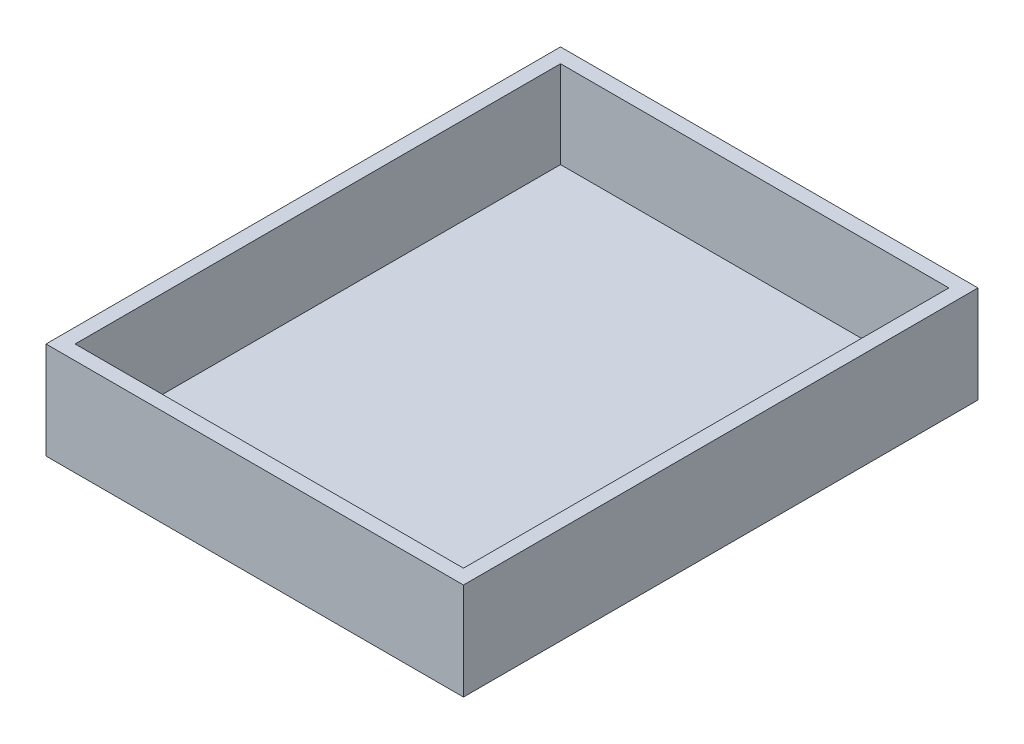
SolidWorks part; units mm, degrees
ref_plane "Front Plane" through (0, 0, 0) normal (0, 0, 1) x (1, 0, 0)
ref_plane "Top Plane" through (0, 0, 0) normal (0, 1, 0) x (1, 0, 0)
ref_plane "Right Plane" through (0, 0, 0) normal (1, 0, 0) x (0, 0, -1)
sketch "Sketch1" plane through (0, 0, 0) normal (0, 1, 0) x (1, 0, 0)
  line L1 (0, 0) -> (101.6, 0)
  line L2 (0, 0) -> (0, 127)
  line L3 (0, 127) -> (101.6, 127)
  line L4 (101.6, 0) -> (101.6, 127)
  dimension "D1" = 127
  dimension "D2" = 101.6
extrude "Base Extrude" add sketch "Sketch1" along normal blind 2.54
sketch "Sketch2" plane through (0, 0, 0) normal (0, -1, 0) x (1, 0, 0)
  line L1 (0, 0) -> (101.6, 0)
  line L2 (0, 0) -> (0, -127)
  line L3 (0, -127) -> (101.6, -127)
  line L4 (101.6, 0) -> (101.6, -127)
  line L5 (-3.81, 3.81) -> (105.41, 3.81)
  line L6 (-3.81, 3.81) -> (-3.81, -130.81)
  line L7 (-3.81, -130.81) -> (105.41, -130.81)
  line L8 (105.41, 3.81) -> (105.41, -130.81)
  dimension "D1" = 3.81
  dimension "D2" = 3.81
  dimension "D3" = 3.81
  dimension "D4" = 3.81
extrude "Walls" add sketch "Sketch2" against normal blind 25.4
